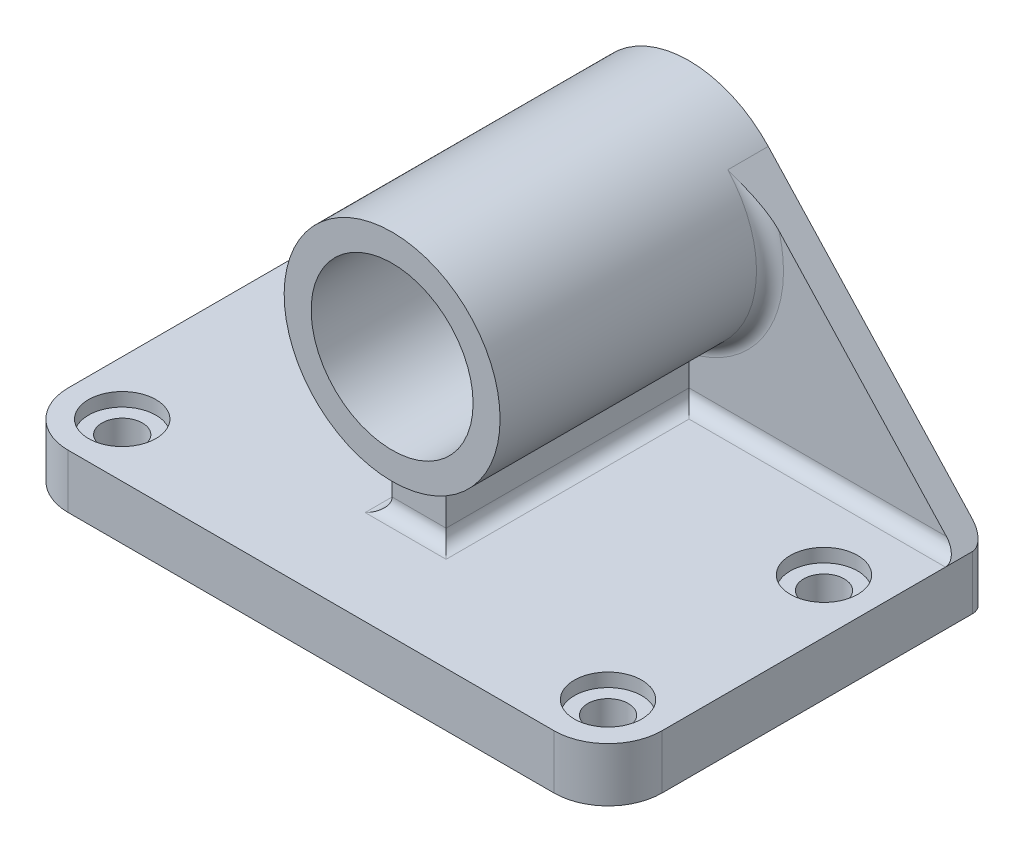
SolidWorks part; units mm, degrees
note: The reader was unsure of these and kept them because the rebuilt part matched: shared geometry of "Sketch4<4>", "Sketch4<5>".
ref_plane "Front Plane" through (0, 0, 0) normal (0, 0, 1) x (1, 0, 0)
ref_plane "Top Plane" through (0, 0, 0) normal (0, 1, 0) x (1, 0, 0)
ref_plane "Right Plane" through (0, 0, 0) normal (1, 0, 0) x (0, 0, -1)
sketch "Sketch2" plane through (0, 0, 0) normal (0, 1, 0) x (1, 0, 0)
  line L0 (0, -6.35) -> (139.7, -6.35)
  line L5 (0, 0) -> (139.7, 0)
  line L6 (0, 0) -> (0, -88.9)
  line L7 (0, -88.9) -> (139.7, -88.9)
  line L8 (139.7, 0) -> (139.7, -88.9)
  line L9 (69.85, 0) -> (69.85, -88.9) construction
  circle A2 centre (127, -25.4) radius 4.7625
  circle A3 centre (127, -76.2) radius 4.7625
  circle A7 centre (12.7, -76.2) radius 4.7625
  circle A8 centre (12.7, -25.4) radius 4.7625
  dimension "D4" = 9.525
  dimension "D5" = 9.525
  dimension "D1" = 88.9
  dimension "D2" = 139.7
  dimension "D3" = 6.35
  dimension "D6" = 25.4
  dimension "D7" = 12.7
  dimension "D8" = 12.7
extrude "Boss-Extrude1" add sketch "Sketch2" along normal blind 12.7
sketch "Sketch3" plane through (0, 12.7, 0) normal (0, 1, 0) x (1, 0, 0)
  line L0 (69.85, 0) -> (69.85, -88.9) construction
  line L1 (0, 0) -> (139.7, 0) construction
  line L2 (0, -88.9) -> (139.7, -88.9) construction
  circle A0 centre (127, -25.4) radius 7.9375
  circle A1 centre (127, -76.2) radius 7.9375
  circle A2 centre (12.7, -76.2) radius 7.9375
  circle A3 centre (12.7, -25.4) radius 7.9375
  dimension "D1" = 15.875
  dimension "D2" = 15.875
extrude "Cut-Extrude1" cut sketch "Sketch3" against normal blind 3.175
sketch "Sketch4" plane through (0, 0, 0) normal (0, 0, 1) x (1, 0, 0)
  line L0 (0, 12.7) -> (51.2051, 68.049)
  line L1 (0, 0) -> (139.7, 0) construction
  line L2 (139.7, 12.7) -> (88.4949, 68.049)
  line L3 (0, 12.7) -> (63.5, 12.7)
  line L4 (0, 12.7) -> (139.7, 12.7) construction
  line L5 (63.5, 12.7) -> (63.5, 26.2066)
  line L6 (76.2, 26.2066) -> (76.2, 12.7)
  line L7 (69.85, 50.8) -> (69.85, 0) construction
  line L8 (76.2, 12.7) -> (139.7, 12.7)
  line L9 (63.5, 12.7) -> (76.2, 12.7)
  circle A0 centre (69.85, 50.8) radius 25.4
  circle A1 centre (69.85, 50.8) radius 19.05
  dimension "D1" = 50.8
  dimension "D2" = 38.1
  dimension "D3" = 50.8
  dimension "D4" = 12.7
extrude "Boss-Extrude2" add sketch "Sketch4" along normal blind 6.35
extrude "Boss-Extrude3" add sketch "Sketch4<4>" along normal blind 69.85
sketch "Sketch4<4>" plane through (0, 0, 0) normal (0, 0, 1) x (1, 0, 0) same geometry as "Sketch4"
extrude "Boss-Extrude4" add sketch "Sketch4<5>" along normal blind 63.5 contours A0 L7 L9 L6 | L7 A0 L5 L9
sketch "Sketch4<5>" plane through (0, 0, 0) normal (0, 0, 1) x (1, 0, 0) same geometry as "Sketch4"
fillet "Fillet1" radius 12.7 2 edges at (139.7, 6.35, 88.9) (0, 6.35, 88.9)
fillet "Fillet2" radius 3.175 2 edges at (139.7, 6.35, 0) (0, 6.35, 0)
fillet "Fillet4" radius 3.175 10 edges at (107.95, 12.7, 6.35) (31.75, 12.7, 6.35) (45.4803, 43.6392, 6.35) (94.2197, 43.6392, 6.35) (69.85, 25.4, 63.5) (69.85, 12.7, 63.5) (63.5, 26.2066, 34.925) (76.2, 26.2066, 34.925) (76.2, 12.7, 34.925) (63.5, 12.7, 34.925)
equation "\"Tube_Diameter\" = \"Hole_Diameter\" + 0.5"
equation "\"Hole_Diameter\"= 1.5"
equation "\"D2@Sketch4\"=\"Hole_Diameter\""
equation "\"D1@Sketch4\"=\"Tube_Diameter\""
equation "\"Part_Width\"= \"Hole_Diameter\" + 4"
equation "\"D2@Sketch2\"=\"Part_Width\""
equation "\"Part_Height\"= \"Hole_Diameter\" / 2 + 1.25"
equation "\"D3@Sketch4\"=\"Part_Height\""
